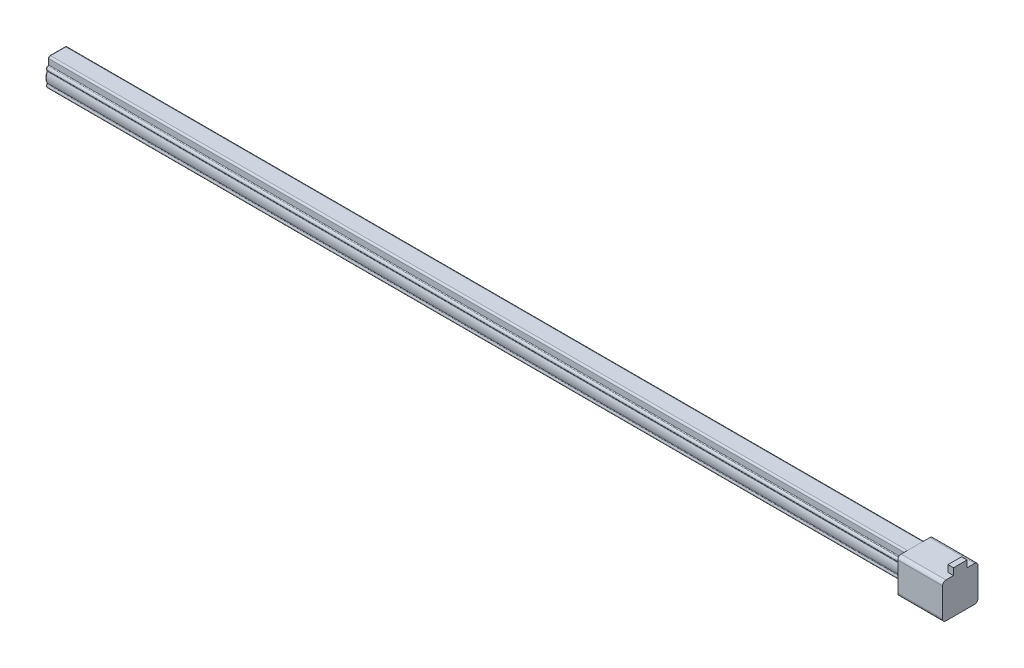
SolidWorks part; units mm, degrees
ref_plane "Спереди" through (0, 0, 0) normal (0, 0, 1) x (1, 0, 0)
ref_plane "Сверху" through (0, 0, 0) normal (0, 1, 0) x (1, 0, 0)
ref_plane "Справа" through (0, 0, 0) normal (1, 0, 0) x (0, 0, -1)
sketch "Эскиз1" plane through (0, 0, 0) normal (0, 0, 1) x (1, 0, 0)
  line L0 (-29, 21) -> (-1045, 21)
  line L1 (24, -21) -> (-24, -21)
  line L2 (24, -21) -> (24, 21)
  line L3 (24, 21) -> (-24, 21)
  line L4 (-24, -21) -> (-24, 21)
  line L5 (24, -21) -> (-24, 21) construction
  line L6 (24, 21) -> (-24, -21) construction
  line L7 (-24, -21) -> (-29, -21)
  line L8 (-24, -21) -> (-24, 21)
  line L9 (-24, 21) -> (-29, 21)
  line L10 (-29, -21) -> (-29, 21)
  line L11 (-1045, 21) -> (-1045, -14)
  line L12 (-1045, -14) -> (-29, -14)
  point P0 (0, 0)
  dimension "D1" = 48
  dimension "D2" = 42
  dimension "D3" = 5
  dimension "D4" = 1016
  dimension "D5" = 35
extrude "Бобышка-Вытянуть1" add sketch "Эскиз1" along normal blind 42 contours L11 L12 L10 L0 | L10 L7 L4 L9 | L4 L1 L2 L3 region at (-537, 3.5, 0) region at (-26.5, 0, 0) region at (0, 0, 0)
sketch "Эскиз2" plane through (0, 0, 42) normal (0, 0, 1) x (1, 0, 0)
  line L0 (-29, -14) -> (-29, 21)
  line L1 (24, 21) -> (-1045, 21) construction
split line "Разделяющая линия1"
sketch "Эскиз3" plane through (0, 21, 0) normal (0, 1, 0) x (1, 0, 0)
  line L1 (-1045, 0) -> (-29, 0)
  line L2 (-1045, 0) -> (-1045, -42)
  line L3 (-1045, -42) -> (-29, -42)
  line L4 (-29, 0) -> (-29, -42)
extrude "Вырез-Вытянуть1" cut sketch "Эскиз3" against normal blind 0.5
fillet "Скругление1" radius 7 4 edges at (-537, -14, 0) (-537, 20.5, 0) (-537, -14, 42) (-537, 20.5, 42)
sketch "Эскиз4" plane through (-1045, 0, 0) normal (-1, 0, 0) x (0, 0, 1)
  line L0 (21, 21) -> (21, -21) construction
  line L1 (42, 21) -> (0, 21) construction
  line L2 (42, -21) -> (0, -21) construction
  circle A0 centre (21, 0) radius 10
  dimension "D1" = 20
extrude "Вырез-Вытянуть2" cut sketch "Эскиз4" against normal up to surface (1016 mm away) up to face at (-29, -14.4832, 21)
sketch "Эскиз5" plane through (-1045, 0, 0) normal (-1, 0, 0) x (0, 0, 1)
  line L1 (32, 7.5) -> (10, 7.5)
  line L2 (32, 7.5) -> (32, 20.5)
  line L3 (32, 20.5) -> (10, 20.5)
  line L4 (0, 13.5) -> (0, -7)
  line L5 (7, -14) -> (35, -14)
  line L6 (42, -7) -> (42, 13.5)
  line L7 (35, 20.5) -> (7, 20.5)
  line L8 (0, 13.5) -> (0, -7)
  line L9 (7, -14) -> (35, -14)
  line L10 (42, -7) -> (42, 13.5)
  line L11 (35, 20.5) -> (7, 20.5)
  line L12 (10, 7.5) -> (10, 20.5)
  line L13 (32, 7.5) -> (10, 20.5) construction
  line L14 (32, 20.5) -> (10, 7.5) construction
  line L15 (32, -8.6603) -> (10, -8.6603)
  line L16 (32, -8.6603) -> (32, 8.6603)
  line L17 (32, 8.6603) -> (10, 8.6603)
  line L18 (10, -8.6603) -> (10, 8.6603)
  line L19 (32, -8.6603) -> (10, 8.6603) construction
  line L20 (32, 8.6603) -> (10, -8.6603) construction
  circle A0 centre (21, 0) radius 14
  circle A1 centre (10, 8.6603) radius 2.5
  circle A2 centre (10, -8.6603) radius 2.5
  circle A3 centre (32, -8.6603) radius 2.5
  circle A4 centre (32, 8.6603) radius 2.5
  arc A5 (0, -7) -> (7, -14) centre (7, -7) ccw
  arc A6 (35, -14) -> (42, -7) centre (35, -7) ccw
  arc A7 (42, 13.5) -> (35, 20.5) centre (35, 13.5) ccw
  arc A8 (7, 20.5) -> (0, 13.5) centre (7, 13.5) ccw
  arc A9 (0, -7) -> (7, -14) centre (7, -7) ccw
  arc A10 (35, -14) -> (42, -7) centre (35, -7) ccw
  arc A11 (42, 13.5) -> (35, 20.5) centre (35, 13.5) ccw
  arc A12 (7, 20.5) -> (0, 13.5) centre (7, 13.5) ccw
  point P5 (21, 14)
  line M11 (0, 13.5) -> (0, -7)
  arc M12 (0, -7) -> (7, -14) centre (7, -7) ccw
  line M13 (7, -14) -> (35, -14)
  arc M14 (35, -14) -> (42, -7) centre (35, -7) ccw
  line M15 (42, -7) -> (42, 13.5)
  arc M16 (42, 13.5) -> (35, 20.5) centre (35, 13.5) ccw
  line M17 (35, 20.5) -> (7, 20.5)
  arc M18 (7, 20.5) -> (0, 13.5) centre (7, 13.5) ccw
  dimension "D3" = 5
  dimension "D2" = 22
  dimension "D1" = 0
extrude "Вырез-Вытянуть3" cut sketch "Эскиз5" against normal up to surface (1016 mm away) contours A0 L12 M17 M18 M11 M12 M13 | A0 L9 L2 M14 M15 M16 M17 region at (-1045, 2.964, 36.9969) region at (-1045, 2.964, 5.0031) up to face at (-29, 18.8166, 21)
fillet "Скругление2" radius 2 2 edges at (-537, 20.5, 10) (-537, 20.5, 32)
fillet "Скругление3" radius 4 4 edges at (-2.5, -21, 0) (-2.5, -21, 42) (-2.5, 21, 0) (-2.5, 21, 42)
fillet "Скругление5" radius 1 20 edges at (-1045, 9.3722, 7.6035) (-1045, -10.2067, 8.0357) (-1045, -10.2067, 33.9643) (-1045, 9.3722, 34.3965) (-1045, 14.8301, 32) (-1045, 19.9142, 31.4142) (-1045, 20.5, 21) (-1045, 19.9142, 10.5858) (-537, 11.1603, 10) (-537, 6.5657, 8.6351) (-537, -6.5657, 8.6351) (-537, -10.4786, 11.7157) (-537, -10.4786, 30.2843) (-537, -6.5657, 33.3649) (-537, 6.5657, 33.3649) (-537, 11.1603, 32) (-1045, -14, 21) (-1045, 0, 7) (-1045, 0, 35) (-1045, 14.8301, 10)
sketch "Эскиз6" plane through (0, 21, 0) normal (0, 1, 0) x (1, 0, 0)
  line L0 (24, -38) -> (24, -4) construction
  line L1 (30.5, -29) -> (17.5, -29)
  line L2 (30.5, -29) -> (30.5, -13)
  line L3 (30.5, -13) -> (17.5, -13)
  line L4 (17.5, -29) -> (17.5, -13)
  line L5 (30.5, -29) -> (17.5, -13) construction
  line L6 (30.5, -13) -> (17.5, -29) construction
  point P0 (24, -21)
  line M3 (24, -38) -> (24, -4)
  dimension "D1" = 13
  dimension "D2" = 16
extrude "Бобышка-Вытянуть2" add sketch "Эскиз6" along normal blind 8 contours L4 L1 L3 M3 region at (20.75, 21, 21)
